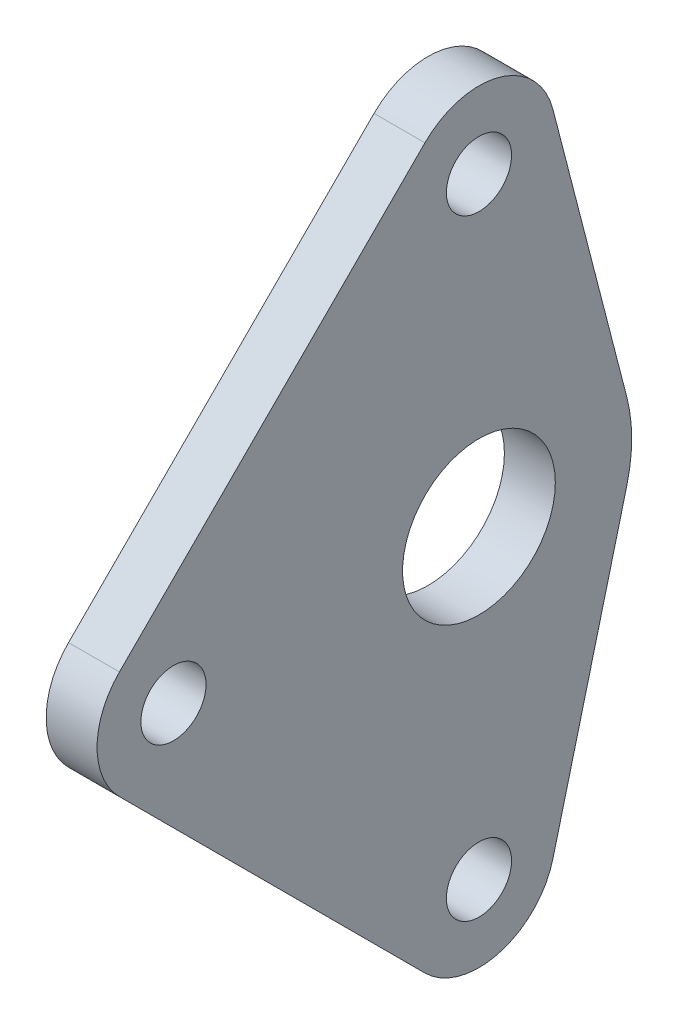
SolidWorks part; units mm, degrees
ref_plane "Front Plane" through (0, 0, 0) normal (0, 0, 1) x (1, 0, 0)
ref_plane "Top Plane" through (0, 0, 0) normal (0, 1, 0) x (1, 0, 0)
ref_plane "Right Plane" through (0, 0, 0) normal (1, 0, 0) x (0, 0, -1)
sketch "Sketch1" plane through (0, 0, 0) normal (1, 0, 0) x (0, 0, -1)
  line L6 (-19.05, 0) -> (0, 0) construction
  line L7 (0, 0) -> (0, 19.05) construction
  line L8 (0, 0) -> (0, -19.05) construction
  line L9 (0, 19.05) -> (-19.05, 0) construction
  line L10 (-19.05, 0) -> (0, -19.05) construction
  line L11 (-3.3676, 22.4176) -> (-22.4176, 3.3676)
  line L12 (-22.4176, -3.3676) -> (-3.3676, -22.4176)
  line L15 (-25.7852, 0) -> (4.7625, -30.5477) construction
  line L16 (4.7625, 0) -> (4.7625, -30.5477) construction
  line L17 (4.7625, 30.5477) -> (-25.7852, 0) construction
  line L18 (4.7625, 0) -> (4.7625, 30.5477) construction
  line L19 (4.6113, 20.2406) -> (9.2225, 2.3813)
  line L20 (9.2225, -2.3813) -> (4.6113, -20.2406)
  circle A10 centre (0, 0) radius 4.7625
  circle A11 centre (0, 19.05) radius 2.032
  circle A12 centre (-19.05, 0) radius 2.032
  circle A13 centre (0, -19.05) radius 2.032
  arc A16 (-22.4176, 3.3676) -> (-22.4176, -3.3676) centre (-19.05, 0) ccw
  arc A17 (9.2225, 2.3813) -> (9.2225, -2.3813) centre (0, 0) cw
  arc A18 (-3.3676, 22.4176) -> (4.6113, 20.2406) centre (0, 19.05) cw
  arc A19 (4.6113, -20.2406) -> (-3.3676, -22.4176) centre (0, -19.05) cw
  dimension "D1" = 9.525
  dimension "D2" = 19.05
  dimension "D5" = 9.525
  dimension "D3" = 4.064
  dimension "D4" = 4.7625
extrude "Boss-Extrude1" add sketch "Sketch1" along normal blind 3.175
